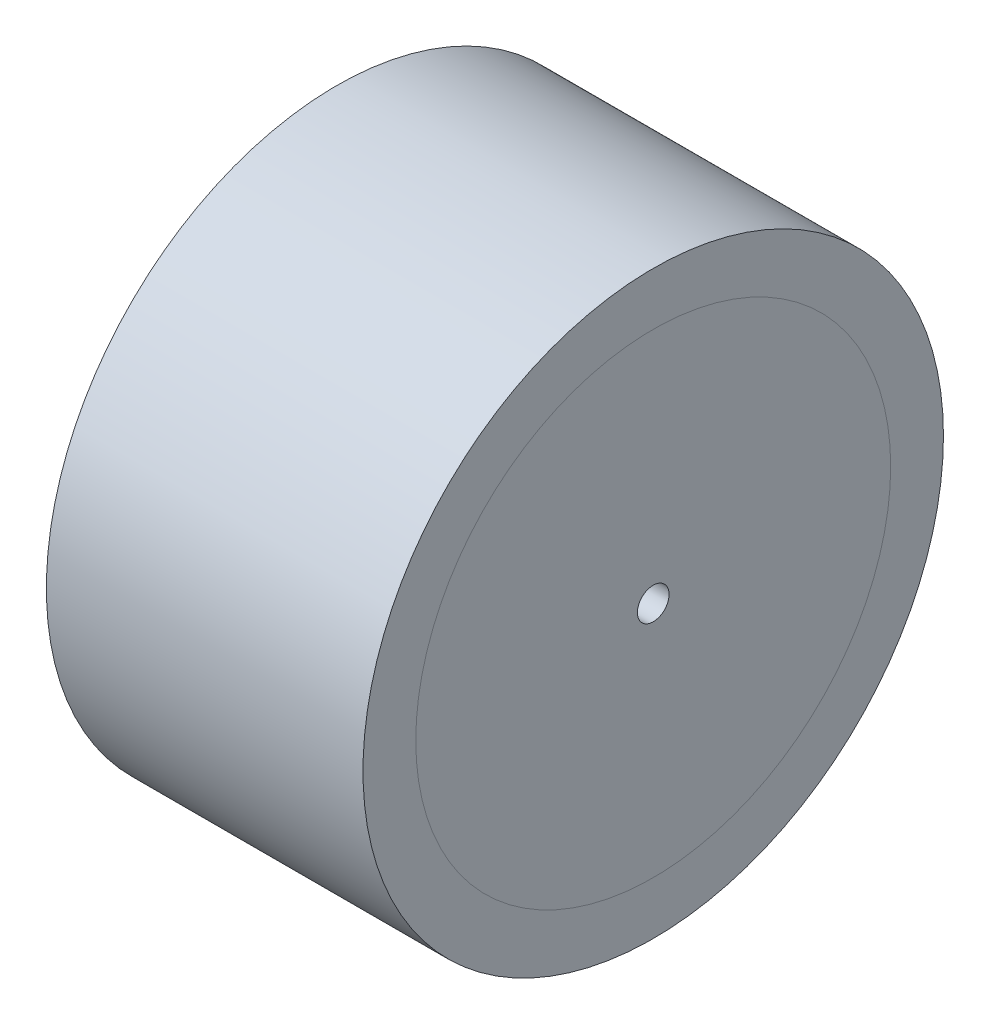
SolidWorks part; units mm, degrees
ref_plane "Front Plane" through (0, 0, 0) normal (0, 0, 1) x (1, 0, 0)
ref_plane "Top Plane" through (0, 0, 0) normal (0, 1, 0) x (1, 0, 0)
ref_plane "Right Plane" through (0, 0, 0) normal (1, 0, 0) x (0, 0, -1)
sketch "Sketch1" plane through (0, 0, 0) normal (1, 0, 0) x (0, 0, -1)
  circle A0 centre (0, 0) radius 27.5
  circle A1 centre (0, 0) radius 22.5
  dimension "D1" = 55
  dimension "D2" = 45
extrude "Boss-Extrude1" add sketch "Sketch1" along normal blind 30 contours A1 | A0 A1 region at (0, 0, 26.7222) region at (0, 0, 0)
split line "Split Line1"
sketch "Sketch1<4>" plane through (0, 0, 0) normal (1, 0, 0) x (0, 0, -1) same geometry as "Sketch1"
sketch "Sketch2" plane through (0, 0, 0) normal (-1, 0, 0) x (0, 0, 1)
  circle A0 centre (0, 0) radius 1.5
  dimension "D1" = 3
extrude "Cut-Extrude1" cut sketch "Sketch2" against normal through all
